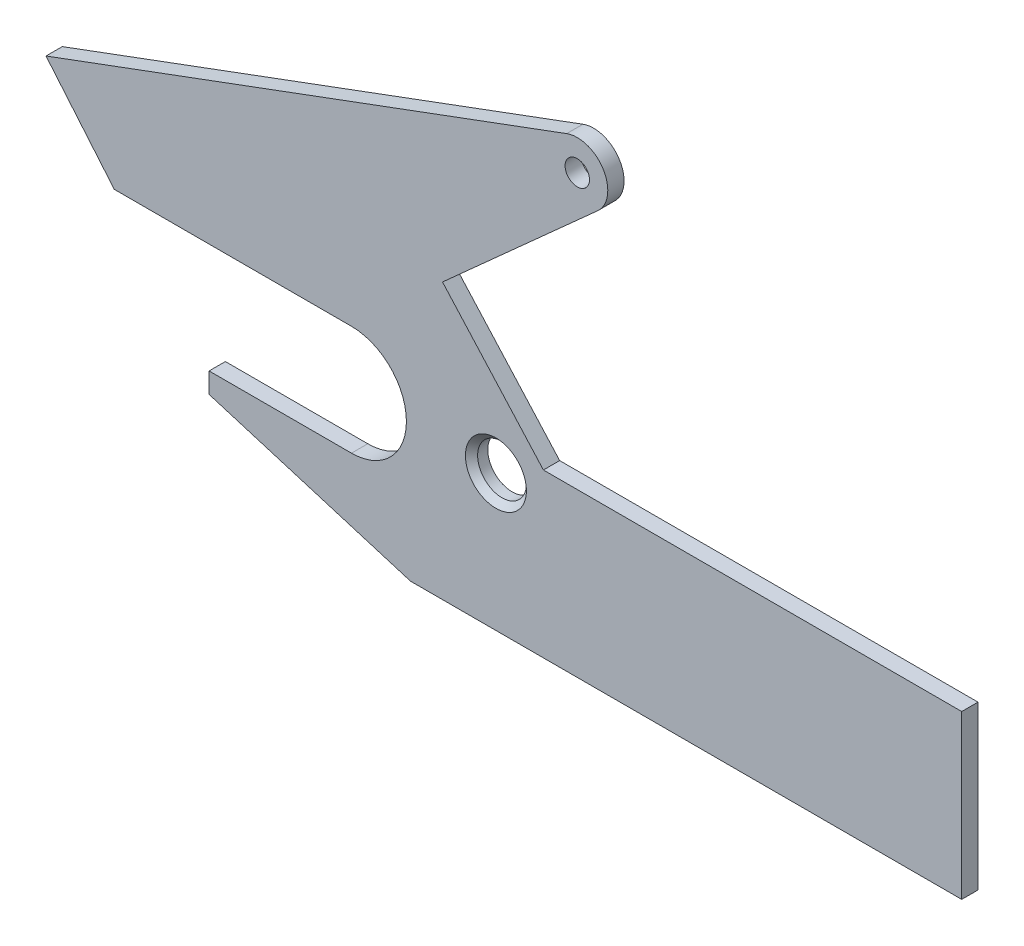
SolidWorks part; units mm, degrees
material "AISI 1020"
ref_plane "Спереди" through (0, 0, 0) normal (0, 0, 1) x (1, 0, 0)
ref_plane "Сверху" through (0, 0, 0) normal (0, 1, 0) x (1, 0, 0)
ref_plane "Справа" through (0, 0, 0) normal (1, 0, 0) x (0, 0, -1)
sketch "Эскиз1" plane through (0, 0, 0) normal (0, 0, 1) x (1, 0, 0)
  line L0 (60.5099, 68.3535) -> (22.3759, 34.1241) construction
  line L1 (22.3759, 34.1241) -> (47.1716, 6.5) construction
  line L2 (47.1716, 6.5) -> (150, 6.5) construction
  line L3 (150, 6.5) -> (150, -33.5) construction
  line L4 (150, -33.5) -> (14.5, -33.5) construction
  line L5 (14.5, -33.5) -> (-35, -18.5) construction
  line L6 (-35, -18.5) -> (-35, -13.5) construction
  line L7 (-35, -13.5) -> (0, -13.5) construction
  line L8 (0, 13.5) -> (-58.3086, 13.5) construction
  line L9 (-58.3086, 13.5) -> (-75.0906, 33.5) construction
  line L10 (-75.0906, 33.5) -> (52.892, 80.9668) construction
  line L11 (60.5099, 68.3535) -> (22.3759, 34.1241)
  line L12 (22.3759, 34.1241) -> (47.1716, 6.5)
  line L13 (47.1716, 6.5) -> (150, 6.5)
  line L14 (150, 6.5) -> (150, -33.5)
  line L15 (150, -33.5) -> (14.5, -33.5)
  line L16 (14.5, -33.5) -> (-35, -18.5)
  line L17 (-35, -18.5) -> (-35, -13.5)
  line L18 (-35, -13.5) -> (0, -13.5)
  line L19 (0, 13.5) -> (-58.3086, 13.5)
  line L20 (-58.3086, 13.5) -> (-75.0906, 33.5)
  line L21 (-75.0906, 33.5) -> (52.892, 80.9668)
  arc A0 (0, -13.5) -> (0, 13.5) centre (0, 0) ccw construction
  arc A1 (60.5099, 68.3535) -> (52.892, 80.9668) centre (55.5, 73.9349) ccw construction
  arc A2 (0, -13.5) -> (0, 13.5) centre (0, 0) ccw
  arc A3 (60.5099, 68.3535) -> (52.892, 80.9668) centre (55.5, 73.9349) ccw
  circle A4 centre (55.5, 73.9349) radius 3 construction
  circle A5 centre (55.5, 73.9349) radius 3
  circle A6 centre (35.5, 0) radius 6 construction
  circle A7 centre (35.5, 0) radius 6
base flange "Базовая кромка1" sketch "Эскиз1" thickness 4 reverse thickness direction yes parameters "D1"=3
chamfer "Фаска1" [suppressed] distance 1.5 angle 45
chamfer "Фаска2" distance 1.5 angle 45 1 edges at (41.5, 0, 4)
sketch "Сгиб-Линии1" [suppressed] plane through (0, 0, 0) normal (0, 1, 0) x (1, 0, 0)
sketch "Граничная рамка1" [suppressed] plane through (0, 0, 0) normal (0, 1, 0) x (1, 0, 0)
sheet metal parameters "Листовой металл3" thickness 4 parameters "D1"=3
flat pattern "Развертка3" [suppressed]
sketch "Сгиб-Линии2" plane through (0, 0, 0) normal (0, 1, 0) x (1, 0, 0)
sketch3d "Граничная рамка2" [suppressed]
  line L0 (130.5906, -107.4349, 0) -> (-94.5, -107.4349, 0) construction
  line L1 (130.5906, 7.5, 0) -> (-94.5, 7.5, 0) construction
  line L2 (130.5906, -107.4349, 0) -> (130.5906, 7.5, 0) construction
  line L3 (-94.5, -107.4349, 0) -> (-94.5, 7.5, 0) construction
